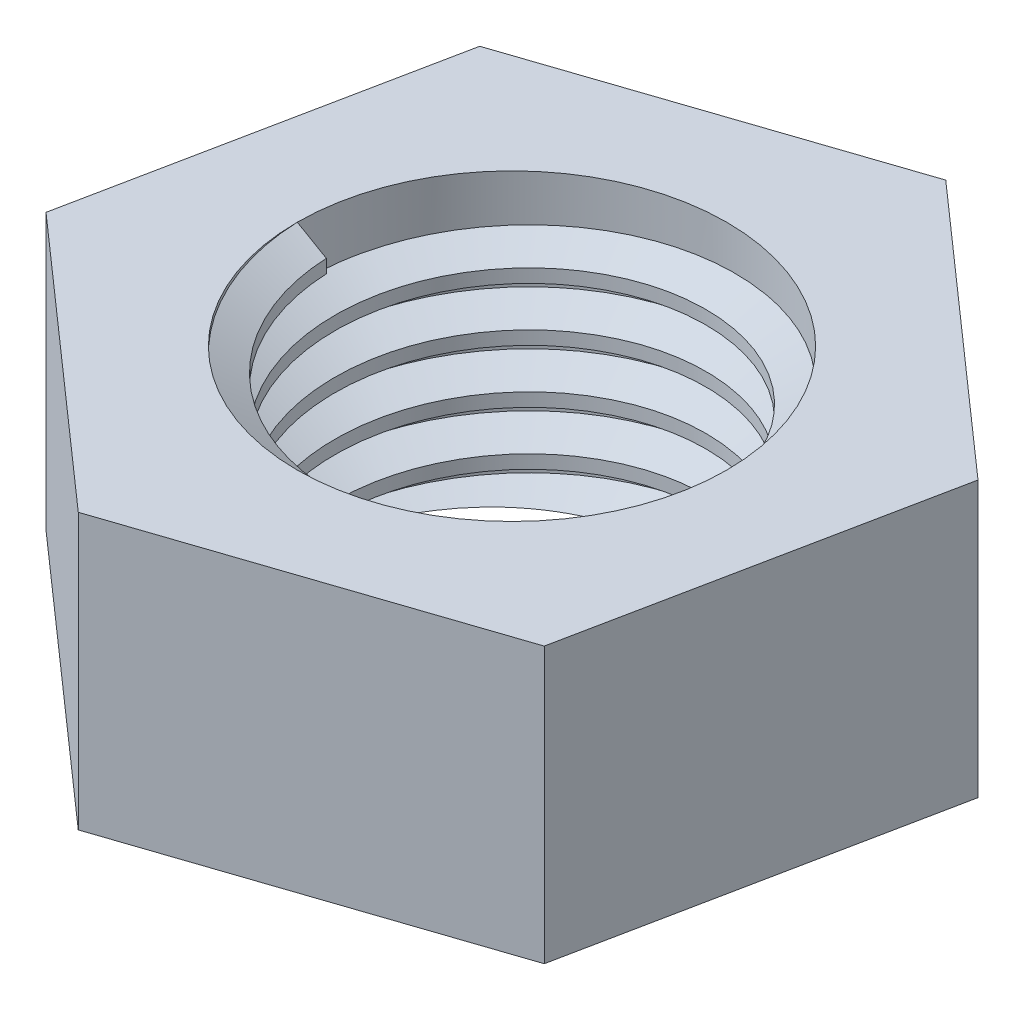
SolidWorks part; units mm, degrees
material "6061 Alloy"
ref_plane "Front Plane" through (0, 0, 0) normal (0, 0, 1) x (1, 0, 0)
ref_plane "Top Plane" through (0, 0, 0) normal (0, 1, 0) x (1, 0, 0)
ref_plane "Right Plane" through (0, 0, 0) normal (1, 0, 0) x (0, 0, -1)
sketch "Sketch1" plane through (0, 0, 0) normal (0, 1, 0) x (1, 0, 0)
  line L1 (20.6366, 6.9263) -> (4.32, 21.3349)
  line L2 (4.32, 21.3349) -> (-16.3166, 14.4087)
  line L3 (-16.3166, 14.4087) -> (-20.6366, -6.9263)
  line L4 (-20.6366, -6.9263) -> (-4.32, -21.3349)
  line L5 (-4.32, -21.3349) -> (16.3166, -14.4087)
  line L6 (16.3166, -14.4087) -> (20.6366, 6.9263)
  circle A0 centre (0, 0) radius 18.8516 construction
  circle A1 centre (0, 0) radius 12.7
  dimension "D1" = 37.7031
extrude "Boss-Extrude1" add sketch "Sketch1" along normal blind 16.2719
thread "Thread1" start angle 0, offset 0, length 0, pitch 3.175, diameter 25.4
ref_plane "Plane1" through (-12.7, 16.2719, 0) normal (0, 0, 1) x (-1, 0, 0)
sketch "Thread Profile1" plane through (-12.7, 16.2719, 0) normal (0, 0, 1) x (-1, 0, 0)
  line L0 (0, 0) -> (0, 3.175) construction
  line L11 (0, 0) -> (0, 2.7781)
  line L12 (0, 2.7781) -> (-1.7185, 1.7859)
  line L13 (-1.7185, 1.7859) -> (-1.7185, 0.9922)
  line L15 (-1.7185, 0.9922) -> (0, 0)
  line L17 (-1.7185, 1.3891) -> (0, 1.3891) construction
  point P2 (0, 0)
  dimension "Pitch" = 3.175
  dimension "Profile_Angle" = 60
  dimension "Profile_Land" = 0.7937
  dimension "Profile_Height" = 1.7185
sketch "Sketch4" plane through (0, 0, 0) normal (0, -1, 0) x (1, 0, 0)
  circle A0 centre (0, 0) radius 15.8719
extrude "Cut-Extrude1" cut sketch "Sketch4" along normal blind 9.4139
